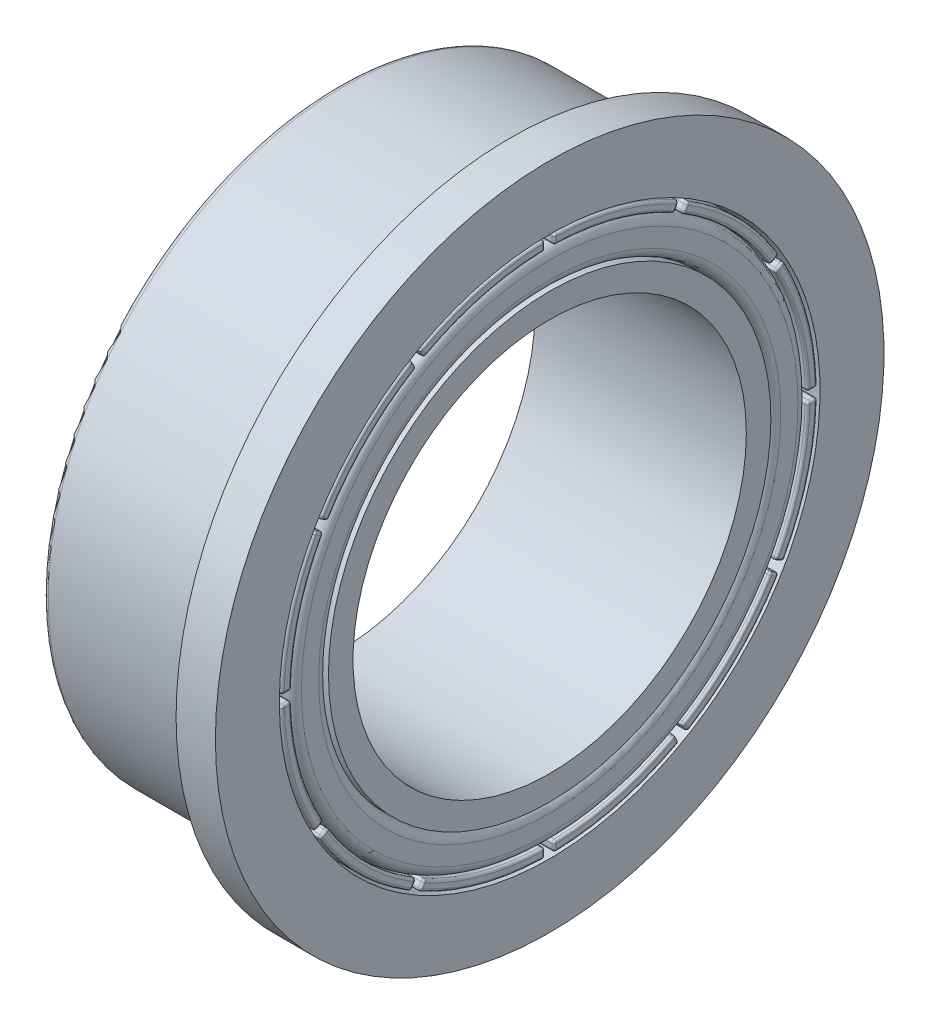
SolidWorks part; units mm, degrees
ref_plane "前视基准面" through (0, 0, 0) normal (0, 0, 1) x (1, 0, 0)
ref_plane "上视基准面" through (0, 0, 0) normal (0, 1, 0) x (1, 0, 0)
ref_plane "右视基准面" through (0, 0, 0) normal (1, 0, 0) x (0, 0, -1)
sketch "草图1" plane through (0, 0, 0) normal (0, 0, 1) x (1, 0, 0)
  line L0 (-6.9125, 0) -> (8.5969, 0) construction
  line L1 (-2.1, 5.5) -> (2.2, 5.5)
  line L2 (2.2, 5.5) -> (2.2, 6.8)
  line L3 (2.2, 6.8) -> (1.4, 6.8)
  line L4 (1.4, 6.8) -> (1.4, 6)
  line L5 (1.4, 6) -> (-2.1, 6)
  line L6 (-2.1, 6) -> (-2.1, 5.5)
  dimension "D1" = 3.5
  dimension "D2" = 0.8
  dimension "D3" = 5.5
  dimension "D4" = 6
  dimension "D5" = 6.8
revolve "旋转1" add sketch "草图1" angle 360 about L0
sketch "草图3" plane through (2.2, 0, 0) normal (1, 0, 0) x (0, 0, -1)
  circle A0 centre (0, 0) radius 4
  circle A1 centre (0, 0) radius 4.5
  dimension "D1" = 8
  dimension "D2" = 9
sketch "草图5" plane through (2.2, 0, 0) normal (1, 0, 0) x (0, 0, -1)
  circle A0 centre (0, 0) radius 4.5
  circle A1 centre (0, 0) radius 5.25
  dimension "D1" = 10.5
extrude "凸台-拉伸4" add sketch "草图5" against normal blind 4.3 separate body
fillet "圆角2" radius 0.2 4 edges at (-2.1, 0, -4.5) (-2.1, 0, -5.25) (2.2, 0, -4.5) (2.2, 0, -5.25)
extrude "凸台-拉伸5" add sketch "草图3" against normal blind 4.3
sketch "草图6" plane through (2.2, 0, 0) normal (1, 0, 0) x (0, 0, -1)
  line L0 (0, 0) -> (8.9618, 4.9676) construction
  line L1 (-11.2804, 0) -> (12.5154, 0) construction
  line L2 (4.5918, 2.5453) -> (4.7667, 2.6422)
  line L4 (0, 0) -> (12.6156, 0.2202) construction
  line L5 (5.2492, 0.0916) -> (5.4492, 0.0951)
  arc A0 (5.4492, 0.0951) -> (4.7667, 2.6422) centre (0, 0) ccw
  arc A1 (5.2492, 0.0916) -> (4.5918, 2.5453) centre (0, 0) ccw
  dimension "D1" = 10.5
  dimension "D3" = 5.45
  dimension "D2" = 29
  dimension "D4" = 1
extrude "凸台-拉伸7" add sketch "草图6" against normal blind 4.3 separate body
ref_axis "基准轴1" through (2.2, 0, 0) along (-1, 0, 0)
fillet "圆角6" radius 0.05 12 edges at (0.05, 2.5453, -4.5918) (0.05, 2.6422, -4.7667) (0.05, 0.0951, -5.4492) (0.05, 0.0916, -5.2492) (-2.1, 0.0934, -5.3492) (-2.1, 1.4106, -5.2643) (-2.1, 2.5937, -4.6792) (-2.1, 1.3588, -5.0711) (2.2, 2.5937, -4.6792) (2.2, 1.4106, -5.2643) (2.2, 0.0934, -5.3492) (2.2, 1.3588, -5.0711)
pattern_circular "阵列(圆周)7" count 12 over 360 about axis through (2.2, 0, 0) along (-1, 0, 0) of bodies 113
fillet "圆角7" radius 0.1 1 edges at (-2.1, 0, 6)
